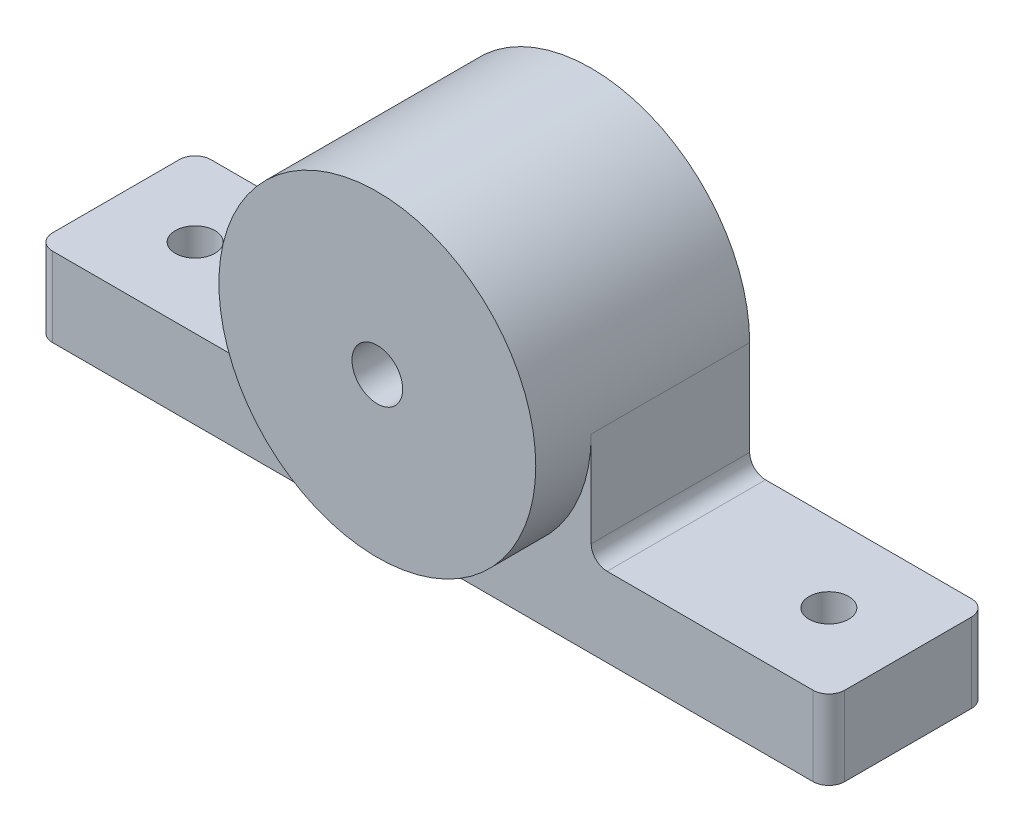
SolidWorks part; units mm, degrees
ref_plane "前视基准面" through (0, 0, 0) normal (0, 0, 1) x (1, 0, 0)
ref_plane "上视基准面" through (0, 0, 0) normal (0, 1, 0) x (1, 0, 0)
ref_plane "右视基准面" through (0, 0, 0) normal (1, 0, 0) x (0, 0, -1)
sketch "草图1" plane through (0, 0, 0) normal (0, 0, 1) x (1, 0, 0)
  circle A0 centre (0, 0) radius 5
  circle A1 centre (0, 0) radius 10
  dimension "D1" = 10
  dimension "D2" = 20
extrude "凸台-拉伸1" add sketch "草图1" along normal blind 7
sketch "草图2" plane through (0, 0, 7) normal (0, 0, 1) x (1, 0, 0)
  circle A0 centre (0, 0) radius 10
  circle A1 centre (0, 0) radius 10 construction
extrude "凸台-拉伸2" add sketch "草图2" along normal blind 5
ref_plane "基准面1" through (0, 0, -1.5) normal (0, 0, -1) x (-1, 0, 0)
sketch "草图3" plane through (0, 0, -1.5) normal (0, 0, -1) x (-1, 0, 0)
  line L0 (-10, 0) -> (-10, -12)
  line L1 (-10, -12) -> (10, -12)
  line L2 (10, -12) -> (10, 0)
  arc A0 (-10, 0) -> (10, 0) centre (0, 0) ccw construction
  circle A1 centre (0, 0) radius 10 construction
  arc A2 (10, 0) -> (-10, 0) centre (0, 0) ccw
  circle A3 centre (0, 0) radius 6
  dimension "D2" = 12
  dimension "D1" = 12
extrude "凸台-拉伸3" add sketch "草图3" against normal blind 10
sketch "草图4" plane through (0, -12, 0) normal (0, -1, 0) x (1, 0, 0)
  line L0 (0, 8.5) -> (0, -1.5) construction
  line L1 (10, 8.5) -> (-10, 8.5) construction
  line L2 (-6.6, -1.5) -> (6.6, -1.5) construction
  line L4 (-25, -1.5) -> (25, -1.5)
  line L5 (-25, -1.5) -> (-25, 8.5)
  line L6 (-25, 8.5) -> (25, 8.5)
  line L7 (25, -1.5) -> (25, 8.5)
  line L8 (-25, -1.5) -> (25, 8.5) construction
  line L9 (-25, 8.5) -> (25, -1.5) construction
  point P7 (0, 3.5)
  dimension "D1" = 50
extrude "凸台-拉伸4" add sketch "草图4" against normal blind 5
fillet "圆角1" radius 1 6 edges at (10, -7, 3.5) (-10, -7, 3.5) (-25, -9.5, 8.5) (-25, -9.5, -1.5) (25, -9.5, -1.5) (25, -9.5, 8.5)
sketch "草图5" plane through (0, -12, 0) normal (0, -1, 0) x (1, 0, 0)
  line L0 (0, 8.5) -> (0, -1.5) construction
  line L1 (10, 8.5) -> (-10, 8.5) construction
  line L2 (-6.6, -1.5) -> (6.6, -1.5) construction
  line L3 (-25, 3.5) -> (25, 3.5) construction
  line L4 (-25, 7.5) -> (-25, -0.5) construction
  line L5 (25, -0.5) -> (25, 7.5) construction
  circle A0 centre (-20, 3.5) radius 1.25
  circle A1 centre (-7.5, 3.5) radius 1.25
  circle A2 centre (7.5, 3.5) radius 1.25
  circle A3 centre (20, 3.5) radius 1.25
  dimension "D1" = 15
  dimension "D2" = 40
  dimension "D3" = 2.5
extrude "切除-拉伸1" cut sketch "草图5" against normal blind 10
cosmetic thread "装饰螺纹线1" parameters "D1"=5, "D2"=3
cosmetic thread "装饰螺纹线2" parameters "D1"=5, "D2"=3
cosmetic thread "装饰螺纹线3" parameters "D1"=5, "D2"=3
cosmetic thread "装饰螺纹线4" parameters "D1"=5, "D2"=3
sketch "草图6" plane through (0, 0, 7) normal (0, 0, -1) x (-1, 0, 0)
  circle A0 centre (0, 0) radius 1.6
  dimension "D1" = 3.2
extrude "切除-拉伸2" cut sketch "草图6" against normal up to next
